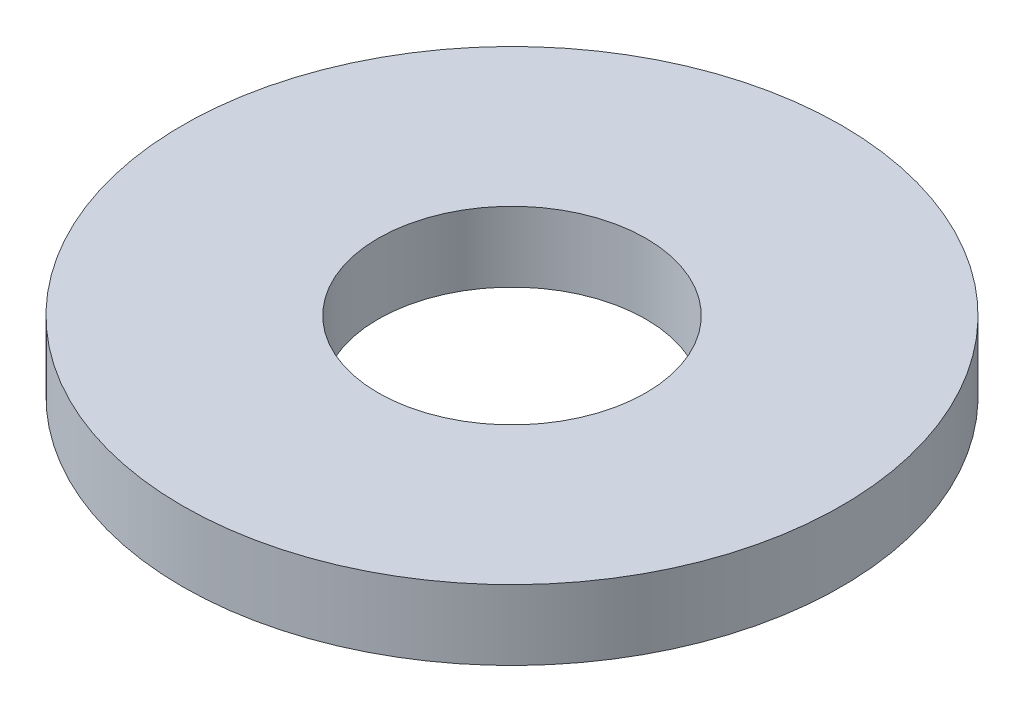
SolidWorks part; units mm, degrees
ref_plane "Front Plane" through (0, 0, 0) normal (0, 0, 1) x (1, 0, 0)
ref_plane "Top Plane" through (0, 0, 0) normal (0, 1, 0) x (1, 0, 0)
ref_plane "Right Plane" through (0, 0, 0) normal (1, 0, 0) x (0, 0, -1)
sketch "Sketch1" plane through (0, 0, 0) normal (0, 1, 0) x (1, 0, 0)
  circle A0 centre (0, 0) radius 80
  dimension "FLANGE_OD" = 160
extrude "Boss-Extrude1" add sketch "Sketch1" along normal blind 17
sketch "Sketch2" plane through (0, 0, 0) normal (0, 1, 0) x (1, 0, 0)
  circle A0 centre (0, 0) radius 32.5
  dimension "BORE_D" = 65
extrude "Cut-Extrude1" cut sketch "Sketch2" along normal through all
sketch "Sketch3" plane through (0, 17, 0) normal (0, 1, 0) x (1, 0, 0)
  circle A0 centre (0, 0) radius 20.9356 construction
  circle A1 centre (-20.9356, 0) radius 2.3597
  dimension "BOLT_D" = 4.7193
  dimension "BOLT_PCD" = 41.8712
extrude "Cut-Extrude2" cut sketch "Sketch3" against normal blind 15.3701 rebuild error yes
pattern_circular "CirPattern1" count 6 over 360 rebuild error yes
